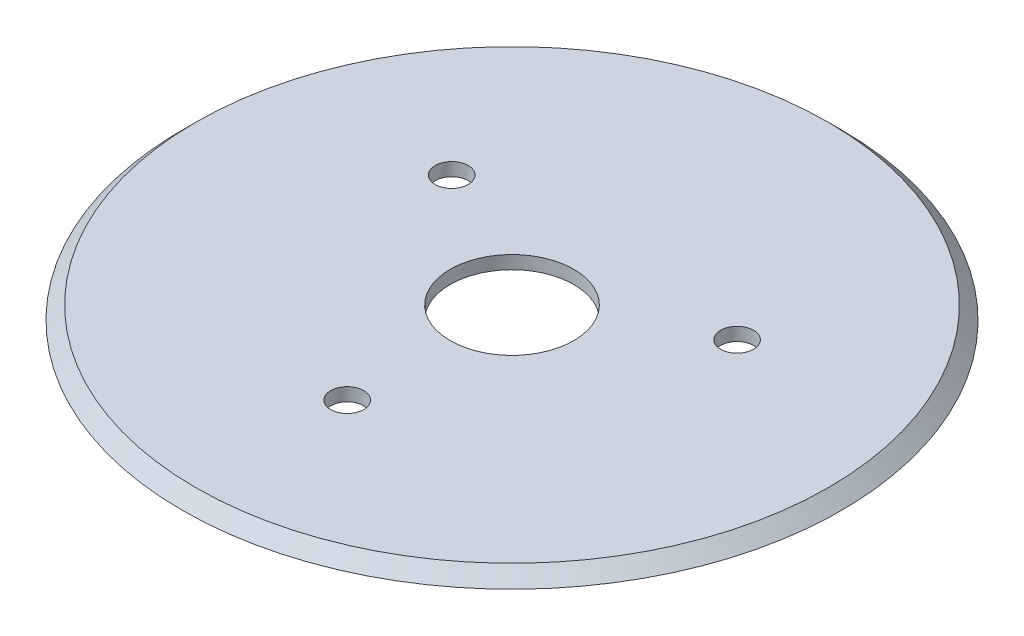
SolidWorks part; units mm, degrees
ref_plane "Front Plane" through (0, 0, 0) normal (0, 0, 1) x (1, 0, 0)
ref_plane "Top Plane" through (0, 0, 0) normal (0, 1, 0) x (1, 0, 0)
ref_plane "Right Plane" through (0, 0, 0) normal (1, 0, 0) x (0, 0, -1)
sketch "Sketch1" plane through (0, 0, 0) normal (0, 1, 0) x (1, 0, 0)
  circle A2 centre (0, 0) radius 40
  dimension "D1" = 80
extrude "Boss-Extrude1" add sketch "Sketch1" along normal blind 1.6
sketch "Sketch3" plane through (0, 0, 0) normal (0, 1, 0) x (1, 0, 0)
  circle A0 centre (0, 0) radius 7.5
  dimension "D1" = 15
extrude "Cut-Extrude1" cut sketch "Sketch3" along normal up to surface (1.6 mm away) up to face at (0, 1.6, 40)
sketch "Sketch5" plane through (0, 0, 0) normal (0, 1, 0) x (1, 0, 0)
  line L1 (0, 0) -> (0, -20) construction
  circle A0 centre (0, -20) radius 2
  circle A7 centre (-17.3205, 10) radius 2
  circle A8 centre (17.3205, 10) radius 2
  point P10 (0, 0)
  point P17 (0, 0)
  dimension "D1" = 4
  dimension "D2" = 20
  dimension "D3" = 3
extrude "Cut-Extrude3" cut sketch "Sketch5" along normal up to surface (1.6 mm away) up to face at (0, 1.6, 7.5)
chamfer "Chamfer1" distance 1.6 angle 45 1 edges at (0, 1.6, 40)
